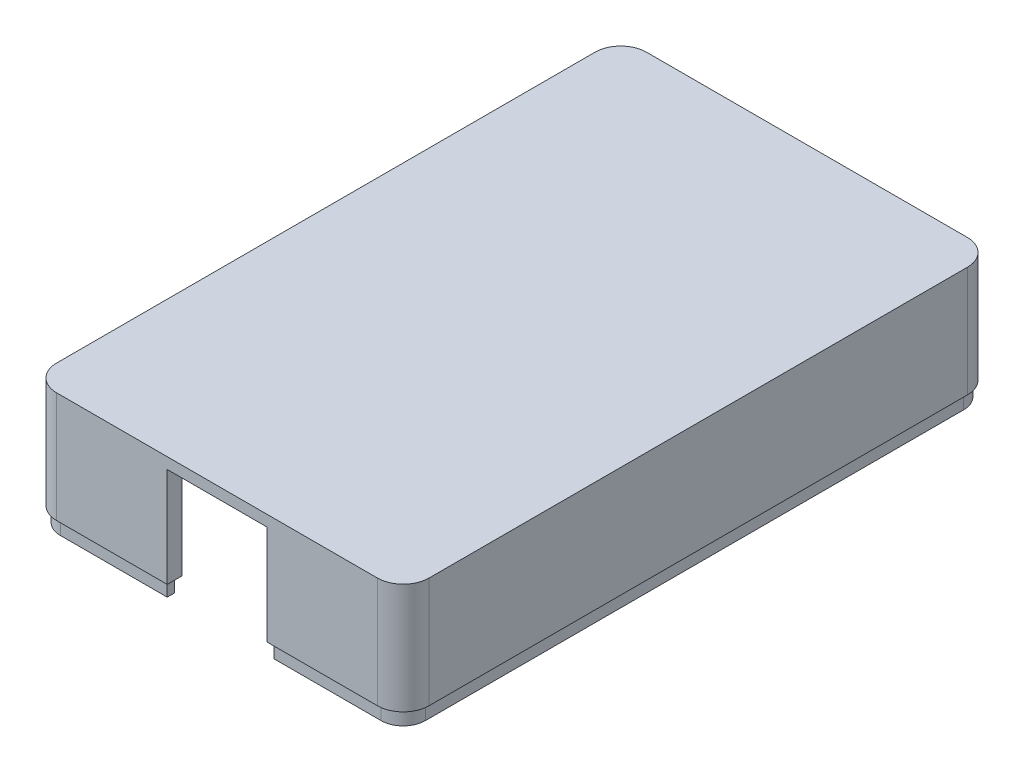
SolidWorks part; units mm, degrees
ref_plane "Alzado" through (0, 0, 0) normal (0, 0, 1) x (1, 0, 0)
ref_plane "Planta" through (0, 0, 0) normal (0, 1, 0) x (1, 0, 0)
ref_plane "Vista lateral" through (0, 0, 0) normal (1, 0, 0) x (0, 0, -1)
sketch "Sketch1" plane through (0, 0, 0) normal (0, 1, 0) x (1, 0, 0)
  line L1 (-21.75, -40) -> (21.75, -40)
  line L2 (-25.25, -36.5) -> (-25.25, 36.5)
  line L3 (-21.75, 40) -> (21.75, 40)
  line L4 (25.25, -36.5) -> (25.25, 36.5)
  line L5 (-25.25, -40) -> (25.25, 40) construction
  line L6 (-25.25, 40) -> (25.25, -40) construction
  arc A0 (-21.75, -40) -> (-25.25, -36.5) centre (-21.75, -36.5) cw
  arc A1 (21.75, -40) -> (25.25, -36.5) centre (21.75, -36.5) ccw
  arc A2 (-25.25, 36.5) -> (-21.75, 40) centre (-21.75, 36.5) cw
  arc A3 (21.75, 40) -> (25.25, 36.5) centre (21.75, 36.5) cw
  point P0 (0, 0)
  dimension "D3" = 3.5
  dimension "D1" = 50.5
  dimension "D2" = 80
extrude "Boss-Extrude1" add sketch "Sketch1" along normal blind 15
sketch "Sketch2" plane through (0, 0, 0) normal (0, -1, 0) x (1, 0, 0)
  line L0 (25.25, 36.5) -> (25.25, -36.5) construction
  line L1 (-19.75, -38) -> (19.75, -38)
  line L2 (-23.25, -34.5) -> (-23.25, 34.5)
  line L3 (-19.75, 38) -> (19.75, 38)
  line L4 (23.25, -34.5) -> (23.25, 34.5)
  line L5 (-23.25, -38) -> (23.25, 38) construction
  line L6 (-23.25, 38) -> (23.25, -38) construction
  line L7 (-21.75, 40) -> (21.75, 40) construction
  arc A0 (19.75, -38) -> (23.25, -34.5) centre (19.75, -34.5) ccw
  arc A1 (-19.75, -38) -> (-23.25, -34.5) centre (-19.75, -34.5) cw
  arc A2 (-23.25, 34.5) -> (-19.75, 38) centre (-19.75, 34.5) cw
  arc A3 (19.75, 38) -> (23.25, 34.5) centre (19.75, 34.5) cw
  point P0 (0, 0)
  dimension "D3" = 3.5
  dimension "D1" = 2
  dimension "D2" = 2
extrude "Cut-Extrude1" cut sketch "Sketch2" against normal blind 13.5
sketch "Sketch3" plane through (0, 0, 40) normal (0, 0, 1) x (1, 0, 0)
  line L0 (0, 0) -> (0, 15) construction
  line L1 (-21.75, 15) -> (21.75, 15) construction
  line L3 (-6.75, 13.5) -> (6.75, 13.5)
  line L4 (-6.75, 13.5) -> (-6.75, -13.5)
  line L5 (-6.75, -13.5) -> (6.75, -13.5)
  line L6 (6.75, 13.5) -> (6.75, -13.5)
  line L7 (-6.75, 13.5) -> (6.75, -13.5) construction
  line L8 (-6.75, -13.5) -> (6.75, 13.5) construction
  dimension "D1" = 1.5
  dimension "D2" = 13.5
extrude "Cut-Extrude2" cut sketch "Sketch3" against normal blind 15
curve "CurvaComp1"
curve "CurvaComp2"
sketch "Croquis2" plane through (0, 0, 0) normal (0, -1, 0) x (1, 0, 0)
  line L0 (-6.75, 40) -> (-6.75, 38) construction
  line L1 (-6.75, 40) -> (-6.75, 38)
  line L4 (-21.75, 40) -> (-6.75, 40) construction
  line L5 (-25.25, -36.5) -> (-25.25, 36.5) construction
  line L6 (21.75, -40) -> (-21.75, -40) construction
  line L7 (25.25, 36.5) -> (25.25, -36.5) construction
  line L8 (6.75, 40) -> (21.75, 40) construction
  line L9 (-21.75, 40) -> (-6.75, 40)
  line L10 (-25.25, -36.5) -> (-25.25, 36.5)
  line L11 (21.75, -40) -> (-21.75, -40)
  line L12 (25.25, 36.5) -> (25.25, -36.5)
  line L13 (6.75, 40) -> (21.75, 40)
  line L14 (-19.75, 38) -> (-6.75, 38) construction
  line L15 (-23.25, -34.5) -> (-23.25, 34.5) construction
  line L16 (19.75, -38) -> (-19.75, -38) construction
  line L17 (23.25, 34.5) -> (23.25, -34.5) construction
  line L19 (-19.75, 38) -> (-6.75, 38)
  line L20 (-23.25, -34.5) -> (-23.25, 34.5)
  line L21 (19.75, -38) -> (-19.75, -38)
  line L22 (23.25, 34.5) -> (23.25, -34.5)
  line L24 (6.75, 38) -> (6.75, 40) construction
  line L25 (6.75, 38) -> (6.75, 40)
  line L26 (19.75, 38) -> (6.75, 38) construction
  line L27 (19.75, 38) -> (6.75, 38)
  arc A0 (-21.75, 40) -> (-25.25, 36.5) centre (-21.75, 36.5) ccw construction
  arc A1 (-25.25, -36.5) -> (-21.75, -40) centre (-21.75, -36.5) ccw construction
  arc A2 (21.75, -40) -> (25.25, -36.5) centre (21.75, -36.5) ccw construction
  arc A3 (25.25, 36.5) -> (21.75, 40) centre (21.75, 36.5) ccw construction
  arc A4 (-21.75, 40) -> (-25.25, 36.5) centre (-21.75, 36.5) ccw
  arc A5 (-25.25, -36.5) -> (-21.75, -40) centre (-21.75, -36.5) ccw
  arc A6 (21.75, -40) -> (25.25, -36.5) centre (21.75, -36.5) ccw
  arc A7 (25.25, 36.5) -> (21.75, 40) centre (21.75, 36.5) ccw
  arc A8 (-19.75, 38) -> (-23.25, 34.5) centre (-19.75, 34.5) ccw construction
  arc A9 (-23.25, -34.5) -> (-19.75, -38) centre (-19.75, -34.5) ccw construction
  arc A10 (19.75, -38) -> (23.25, -34.5) centre (19.75, -34.5) ccw construction
  arc A11 (23.25, 34.5) -> (19.75, 38) centre (19.75, 34.5) ccw construction
  arc A12 (-19.75, 38) -> (-23.25, 34.5) centre (-19.75, 34.5) ccw
  arc A13 (-23.25, -34.5) -> (-19.75, -38) centre (-19.75, -34.5) ccw
  arc A14 (19.75, -38) -> (23.25, -34.5) centre (19.75, -34.5) ccw
  arc A15 (23.25, 34.5) -> (19.75, 38) centre (19.75, 34.5) ccw
sketch "Croquis3" plane through (0, 0, 0) normal (0, -1, 0) x (1, 0, 0)
  line L12 (7.25, 38.5) -> (19.75, 38.5)
  line L13 (7.25, 38.5) -> (19.75, 38.5)
  line L14 (7.25, 39.5) -> (7.25, 38.5)
  line L15 (7.25, 39.5) -> (7.25, 38.5)
  line L24 (-24.75, 36.5) -> (-24.75, -36.5)
  line L25 (-7.25, 39.5) -> (-21.75, 39.5)
  line L26 (-7.25, 38.5) -> (-7.25, 39.5)
  line L27 (-19.75, 38.5) -> (-7.25, 38.5)
  line L28 (-23.75, -34.5) -> (-23.75, 34.5)
  line L29 (19.75, -38.5) -> (-19.75, -38.5)
  line L30 (23.75, 34.5) -> (23.75, -34.5)
  line L33 (21.75, 39.5) -> (7.25, 39.5)
  line L34 (24.75, -36.5) -> (24.75, 36.5)
  line L35 (-21.75, -39.5) -> (21.75, -39.5)
  line L36 (-24.75, 36.5) -> (-24.75, -36.5)
  line L37 (-7.25, 39.5) -> (-21.75, 39.5)
  line L38 (-7.25, 38.5) -> (-7.25, 39.5)
  line L39 (-19.75, 38.5) -> (-7.25, 38.5)
  line L40 (-23.75, -34.5) -> (-23.75, 34.5)
  line L41 (19.75, -38.5) -> (-19.75, -38.5)
  line L42 (23.75, 34.5) -> (23.75, -34.5)
  line L45 (21.75, 39.5) -> (7.25, 39.5)
  line L46 (24.75, -36.5) -> (24.75, 36.5)
  line L47 (-21.75, -39.5) -> (21.75, -39.5)
  arc A16 (-21.75, 39.5) -> (-24.75, 36.5) centre (-21.75, 36.5) ccw
  arc A17 (-19.75, 38.5) -> (-23.75, 34.5) centre (-19.75, 34.5) ccw
  arc A18 (-23.75, -34.5) -> (-19.75, -38.5) centre (-19.75, -34.5) ccw
  arc A19 (19.75, -38.5) -> (23.75, -34.5) centre (19.75, -34.5) ccw
  arc A20 (23.75, 34.5) -> (19.75, 38.5) centre (19.75, 34.5) ccw
  arc A21 (24.75, 36.5) -> (21.75, 39.5) centre (21.75, 36.5) ccw
  arc A22 (21.75, -39.5) -> (24.75, -36.5) centre (21.75, -36.5) ccw
  arc A23 (-24.75, -36.5) -> (-21.75, -39.5) centre (-21.75, -36.5) ccw
  arc A24 (-21.75, 39.5) -> (-24.75, 36.5) centre (-21.75, 36.5) ccw
  arc A25 (-19.75, 38.5) -> (-23.75, 34.5) centre (-19.75, 34.5) ccw
  arc A26 (-23.75, -34.5) -> (-19.75, -38.5) centre (-19.75, -34.5) ccw
  arc A27 (19.75, -38.5) -> (23.75, -34.5) centre (19.75, -34.5) ccw
  arc A28 (23.75, 34.5) -> (19.75, 38.5) centre (19.75, 34.5) ccw
  arc A29 (24.75, 36.5) -> (21.75, 39.5) centre (21.75, 36.5) ccw
  arc A30 (21.75, -39.5) -> (24.75, -36.5) centre (21.75, -36.5) ccw
  arc A31 (-24.75, -36.5) -> (-21.75, -39.5) centre (-21.75, -36.5) ccw
  dimension "D1" = 0.5
extrude "Saliente-Extruir1" add sketch "Croquis3" along normal blind 2
